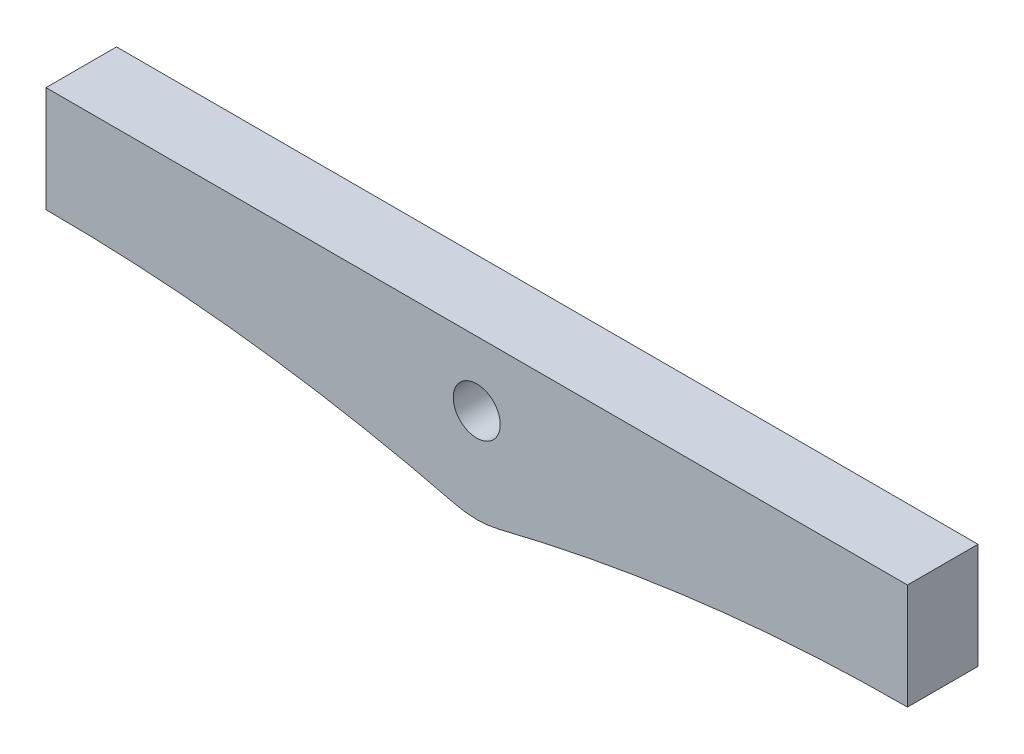
SolidWorks part; units mm, degrees
ref_plane "Front Plane" through (0, 0, 0) normal (0, 0, 1) x (1, 0, 0)
ref_plane "Top Plane" through (0, 0, 0) normal (0, 1, 0) x (1, 0, 0)
ref_plane "Right Plane" through (0, 0, 0) normal (1, 0, 0) x (0, 0, -1)
sketch "Sketch1" plane through (0, 0, 0) normal (0, 0, 1) x (1, 0, 0)
  line L0 (-36.65, 1) -> (36.65, 1) construction
  line L5 (0, 0) -> (0, 1) construction
  line L7 (-36.65, -3.5) -> (36.65, -3.5)
  line L8 (-36.65, -3.5) -> (-36.65, 5.5)
  line L9 (-36.65, 5.5) -> (36.65, 5.5)
  line L10 (36.65, -3.5) -> (36.65, 5.5)
  line L11 (-36.65, -3.5) -> (36.65, 5.5) construction
  line L12 (-36.65, 5.5) -> (36.65, -3.5) construction
  circle A0 centre (0, 0) radius 2
  arc A1 (1.9354, -7.7624) -> (-1.9354, -7.7624) centre (0, 0) cw
  arc A2 (-36.65, -3.5) -> (-1.9354, -7.7624) centre (-36.65, -146.9969) cw
  arc A3 (36.65, -3.5) -> (1.9354, -7.7624) centre (36.65, -146.9969) ccw
  point P14 (7.1561, -4.3906)
  point P15 (0, 0)
  point P16 (0, 0)
  point P17 (0, 0)
  dimension "D3" = 4
  dimension "D4" = 6
  dimension "D1" = 4.5
  dimension "D2" = 73.3
  dimension "D5" = 1
extrude "Boss-Extrude1" add sketch "Sketch1" along normal blind 6 contours L7 L10 L9 L8 | A3 L7 A2 A1 A0 region at (-35.9115, 1, 0) region at (0, -4.9144, 0)
